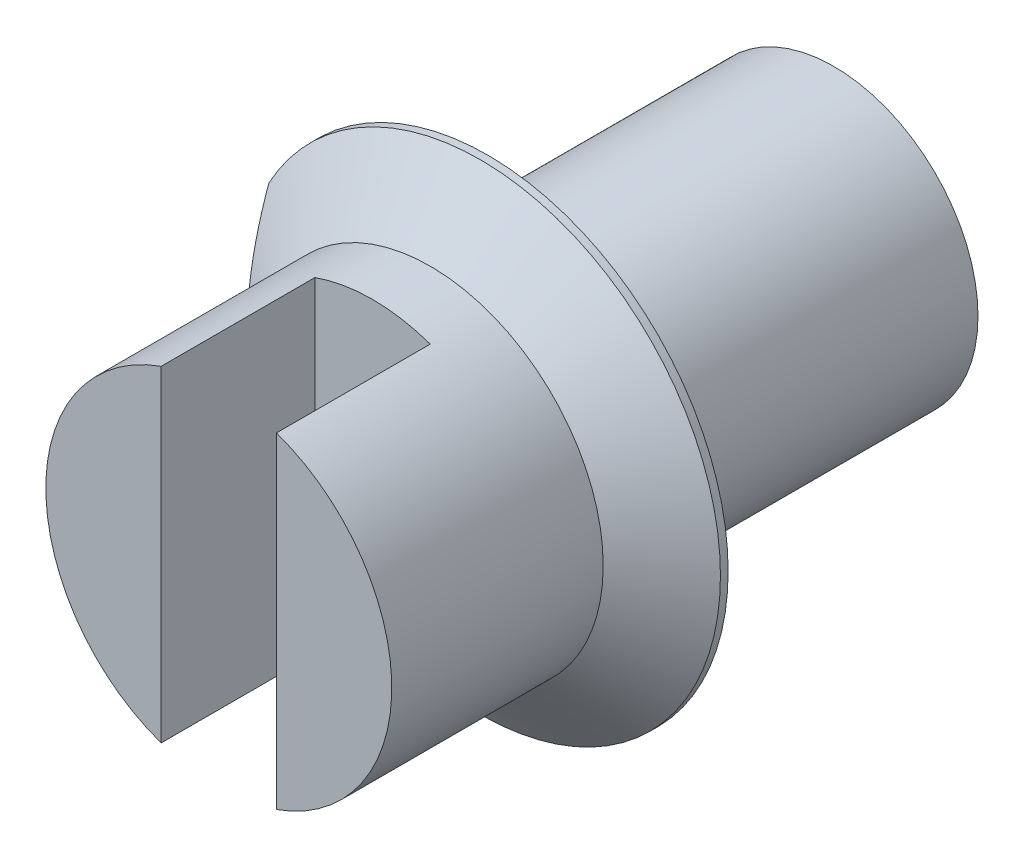
SolidWorks part; units mm, degrees
ref_plane "Alzado" through (0, 0, 0) normal (0, 0, 1) x (1, 0, 0)
ref_plane "Planta" through (0, 0, 0) normal (0, 1, 0) x (1, 0, 0)
ref_plane "Vista lateral" through (0, 0, 0) normal (1, 0, 0) x (0, 0, -1)
sketch "Sketch1" plane through (0, 0, 0) normal (0, 0, 1) x (1, 0, 0)
  circle A0 centre (0, 0) radius 0.375
  dimension "D1" = 0.75
extrude "Boss-Extrude1" add sketch "Sketch1" against normal blind 0.9
sketch "Sketch2" plane through (0, 0, 0) normal (0, 0, 1) x (1, 0, 0)
  circle A0 centre (0, 0) radius 0.625
  dimension "D1" = 1.25
extrude "Boss-Extrude2" add sketch "Sketch2" along normal blind 0.15
sketch "Sketch3" plane through (0, 0, 0.15) normal (0, 0, 1) x (1, 0, 0)
  circle A0 centre (0, 0) radius 0.45
  dimension "D1" = 0.9
extrude "Boss-Extrude3" add sketch "Sketch3" along normal blind 0.55
sketch "Sketch4" plane through (0, 0, 0.7) normal (0, 0, 1) x (1, 0, 0)
  line L0 (0, -1000) -> (0, 49000) construction
  line L1 (0.15, -999.9943) -> (0.15, 49000.0057) construction
  line L2 (-0.15, -1000.0088) -> (-0.15, 48999.9912) construction
  line L4 (-0.15, 0.7355) -> (0.15, 0.7355)
  line L5 (-0.15, 0.7355) -> (-0.15, -0.7786)
  line L6 (-0.15, -0.7786) -> (0.15, -0.7786)
  line L7 (0.15, 0.7355) -> (0.15, -0.7786)
  dimension "D1" = 0.15
  dimension "D2" = 0.15
extrude "Cut-Extrude1" cut sketch "Sketch4" against normal blind 0.4
chamfer "Chamfer1" distance 0.13 distance2 0.175 1 edges at (0.625, 0, 0.15) first distance on face at (0.625, 0, 0.15)
sketch "Sketch5" plane through (0, 0, 0) normal (0, 0, 1) x (1, 0, 0)
  line L0 (0, -1000) -> (0, 49000) construction
  line L1 (-0.55, -999.9887) -> (-0.55, 49000.0113) construction
  line L3 (-0.9556, 0.7942) -> (-0.55, 0.7942)
  line L4 (-0.9556, 0.7942) -> (-0.9556, -0.7923)
  line L5 (-0.9556, -0.7923) -> (-0.55, -0.7923)
  line L6 (-0.55, 0.7942) -> (-0.55, -0.7923)
  dimension "D1" = 0.55
extrude "Cut-Extrude2" cut sketch "Sketch5" against normal through all both and the other way through all
